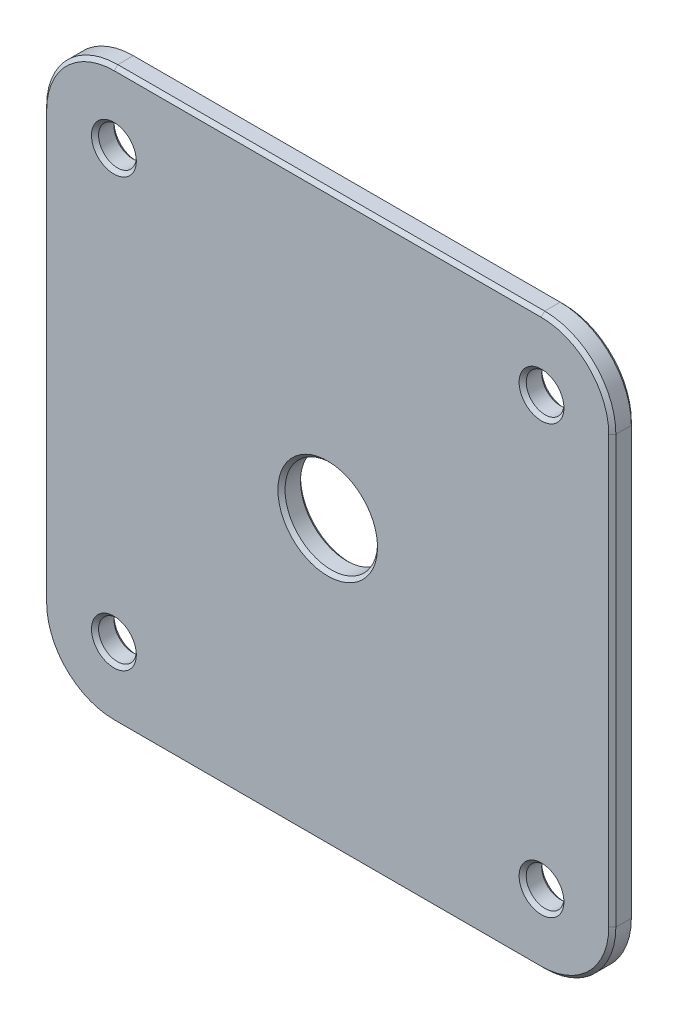
SolidWorks part; units mm, degrees
ref_plane "Front Plane" through (0, 0, 0) normal (0, 0, 1) x (1, 0, 0)
ref_plane "Top Plane" through (0, 0, 0) normal (0, 1, 0) x (1, 0, 0)
ref_plane "Right Plane" through (0, 0, 0) normal (1, 0, 0) x (0, 0, -1)
sketch "Sketch1" plane through (0, 0, 0) normal (0, 0, 1) x (1, 0, 0)
  line L1 (-40, -40) -> (40, -40)
  line L2 (-40, -40) -> (-40, 40)
  line L3 (-40, 40) -> (40, 40)
  line L4 (40, -40) -> (40, 40)
  line L5 (-40, -40) -> (40, 40) construction
  line L6 (-40, 40) -> (40, -40) construction
  point P0 (0, 0)
  dimension "D1" = 80
extrude "1/8 Inch Sheet" add sketch "Sketch1" along normal mid plane 3.175
sketch "Sketch4" plane through (0, 0, -1.5875) normal (0, 0, -1) x (-1, 0, 0)
  line L0 (-40, -40) -> (40, 40) construction
  line L2 (-40, 40) -> (40, -40) construction
  line L3 (40, -40) -> (-40, -40) construction
  circle A0 centre (0, 0) radius 42.5 construction
  point P19 (30.052, 30.052)
  point P21 (-30.052, 30.052)
  point P23 (-30.052, -30.052)
  point P25 (30.052, -30.052)
  dimension "D1" = 85
hole_wizard "M5 Clearance Hole1" positions "Sketch4" profile "Sketch3" hole size "M5" standard "ANSI Metric" end condition through all
sketch "Sketch3" plane through (-30.052, -30.052, -1.5875) normal (1, 0, 0) x (0, 1, 0)
  line L0 (0, 0) -> (0, 3.175)
  line L1 (0, 3.175) -> (2.65, 3.175)
  line L2 (2.65, 3.175) -> (2.65, 0)
  line L5 (2.65, 0) -> (0, 0)
  line L11 (0, -6.35) -> (0, 107.95) construction
  dimension "Thru Hole Dia." = 5.3
  dimension "Thru Hole Depth" = 3.175
sketch "Sketch7" plane through (0, 0, 1.5875) normal (0, 0, 1) x (1, 0, 0)
  point P0 (0, 0)
hole_wizard "M12 Clearance Hole1" positions "Sketch7" profile "Sketch6" hole size "M12" standard "ANSI Metric" end condition through all
sketch "Sketch6" plane through (0, 0, 1.5875) normal (1, 0, 0) x (0, -1, 0)
  line L0 (0, 0) -> (0, 3.175)
  line L1 (0, 3.175) -> (6.5, 3.175)
  line L2 (6.5, 3.175) -> (6.5, 0)
  line L5 (6.5, 0) -> (0, 0)
  line L11 (0, -6.35) -> (0, 107.95) construction
  dimension "Thru Hole Dia." = 13
  dimension "Thru Hole Depth" = 3.175
fillet "Fillet1 - 10mm" radius 10 4 edges at (40, -40, 0) (-40, -40, 0) (-40, 40, 0) (40, 40, 0)
chamfer "Chamfer1 - 0.5mm" distance 0.5 angle 45 26 edges at (-37.0711, -37.0711, 1.5875) (-40, 0, 1.5875) (-37.0711, 37.0711, 1.5875) (0, 40, 1.5875) (37.0711, 37.0711, 1.5875) (40, 0, 1.5875) (37.0711, -37.0711, 1.5875) (0, -40, 1.5875) (-32.702, -30.052, 1.5875) (27.402, -30.052, 1.5875) (27.402, 30.052, 1.5875) (-32.702, 30.052, 1.5875) (6.5, 0, 1.5875) (37.0711, 37.0711, -1.5875) (0, 40, -1.5875) (-37.0711, 37.0711, -1.5875) (-40, 0, -1.5875) (-37.0711, -37.0711, -1.5875) (0, -40, -1.5875) (37.0711, -37.0711, -1.5875) (40, 0, -1.5875) (-32.702, -30.052, -1.5875) (27.402, -30.052, -1.5875) (27.402, 30.052, -1.5875) (-32.702, 30.052, -1.5875) (6.5, 0, -1.5875)
